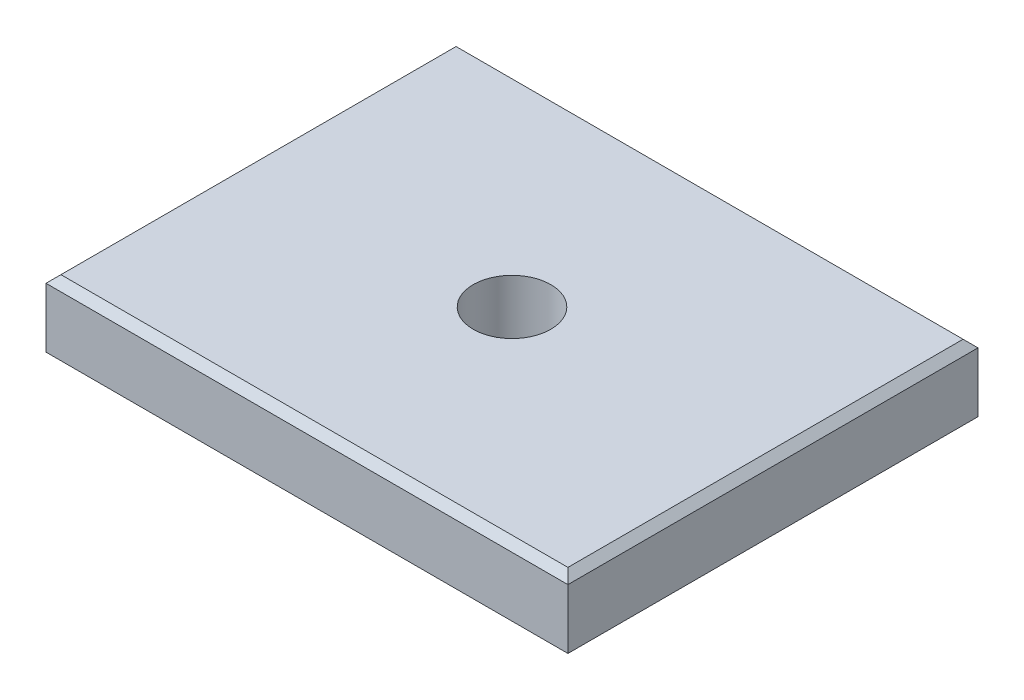
SolidWorks part; units mm, degrees
material "Plain Carbon Steel"
ref_plane "Front Plane" through (0, 0, 0) normal (0, 0, 1) x (1, 0, 0)
ref_plane "Top Plane" through (0, 0, 0) normal (0, 1, 0) x (1, 0, 0)
ref_plane "Right Plane" through (0, 0, 0) normal (1, 0, 0) x (0, 0, -1)
sketch "Sketch1" plane through (0, 0, 0) normal (0, 1, 0) x (1, 0, 0)
  line L1 (-35, -27.5) -> (35, -27.5)
  line L2 (-35, -27.5) -> (-35, 27.5)
  line L3 (-35, 27.5) -> (35, 27.5)
  line L4 (35, -27.5) -> (35, 27.5)
  line L5 (-35, -27.5) -> (35, 27.5) construction
  line L6 (-35, 27.5) -> (35, -27.5) construction
  point P0 (0, 0)
  dimension "D1" = 70
  dimension "D2" = 55
extrude "Boss-Extrude1" add sketch "Sketch1" against normal blind 10
chamfer "Chamfer1" distance 1 angle 45 8 edges at (0, -10, -27.5) (-35, -10, 0) (0, -10, 27.5) (35, -10, 0) (0, 0, 27.5) (-35, 0, 0) (0, 0, -27.5) (35, 0, 0)
sketch "Sketch2" plane through (0, 0, 0) normal (0, 1, 0) x (1, 0, 0)
  circle A0 centre (0, 0) radius 5.2
  dimension "D1" = 10.4
extrude "Cut-Extrude1" cut sketch "Sketch2" against normal through all
